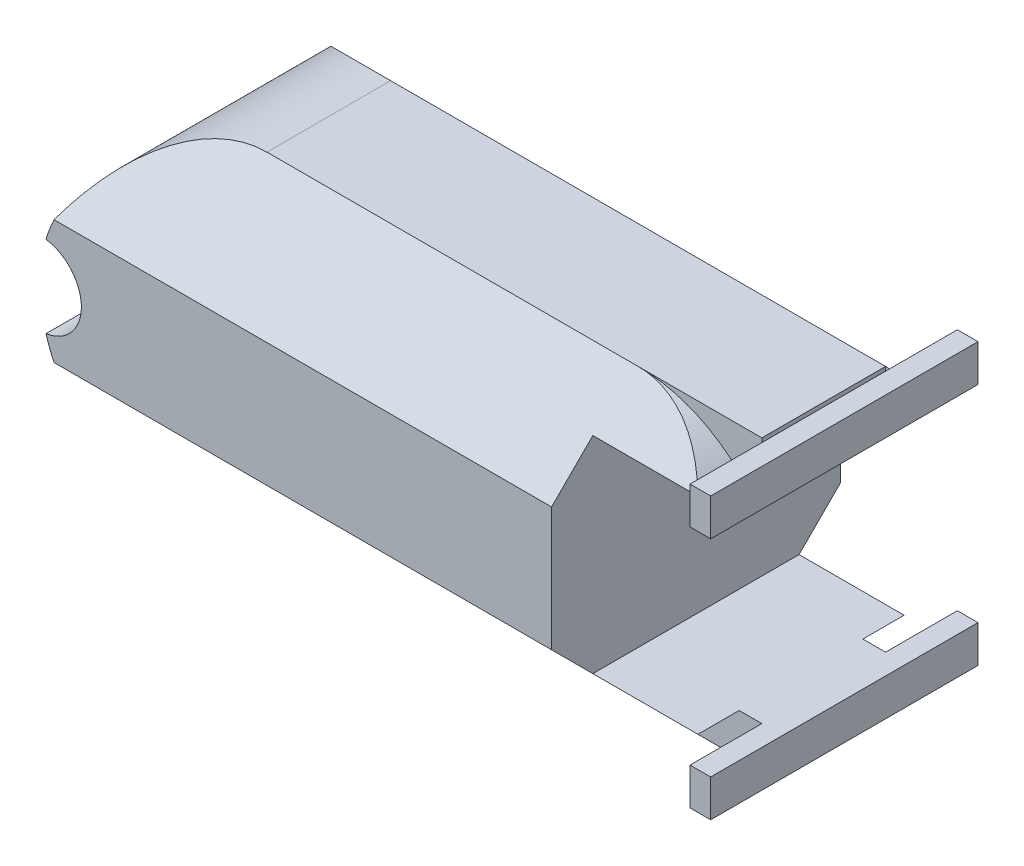
SolidWorks part; units mm, degrees
ref_plane "Ön Düzlem" through (0, 0, 0) normal (0, 0, 1) x (1, 0, 0)
ref_plane "Üst Düzlem" through (0, 0, 0) normal (0, 1, 0) x (1, 0, 0)
ref_plane "Sağ Düzlem" through (0, 0, 0) normal (1, 0, 0) x (0, 0, -1)
sketch "Çizim1" plane through (0, 0, 0) normal (0, 0, 1) x (1, 0, 0)
  line L1 (-40, 17.5) -> (40, 17.5)
  line L2 (-40, 17.5) -> (-40, -17.5)
  line L3 (-40, -17.5) -> (40, -17.5)
  line L4 (40, 17.5) -> (40, -17.5)
  line L5 (-40, 17.5) -> (40, -17.5) construction
  line L6 (-40, -17.5) -> (40, 17.5) construction
  point P0 (0, 0)
  dimension "D1" = 35
  dimension "D2" = 80
extrude "Yükseklik-Ekstrüzyon1" add sketch "Çizim1" along normal blind 35
fillet "Radyus1" radius 17.5 1 edges at (-40, 17.5, 17.5)
fillet "Radyus2" radius 17.5 1 edges at (-40, -17.5, 17.5)
fillet "Radyus3" radius 17.5 2 edges at (40, -17.5, 17.5) (40, 17.5, 17.5)
sketch "Çizim2" plane through (0, 0, 35) normal (0, 0, 1) x (1, 0, 0)
  circle A0 centre (-40, 0) radius 5
  dimension "D1" = 10
extrude "Kes-Ekstrüzyon1" cut sketch "Çizim2" against normal through all
chamfer "Pah1" distance 10 angle 45 4 edges at (0, 17.5, 35) (0, -17.5, 35) (0, -17.5, 0) (0, 17.5, 0) tangent propagation no
sketch "Çizim3" plane through (0, 17.5, 0) normal (0, 1, 0) x (1, 0, 0)
  line L0 (22.5, -10) -> (-22.5, -10) construction
  line L1 (0, -10) -> (37.5, -10)
  line L2 (0, -10) -> (0, -25)
  line L3 (0, -25) -> (37.5, -25)
  line L4 (37.5, -10) -> (37.5, -25)
  dimension "D1" = 37.5
extrude "Yükseklik-Ekstrüzyon2" add sketch "Çizim3" against normal blind 5
sketch "Çizim4" plane through (0, -17.5, 0) normal (0, -1, 0) x (1, 0, 0)
  line L0 (22.5, 25) -> (-22.5, 25) construction
  line L1 (0, 25) -> (37.5, 25)
  line L2 (0, 25) -> (0, 10)
  line L3 (0, 10) -> (37.5, 10)
  line L4 (37.5, 25) -> (37.5, 10)
  dimension "D1" = 37.5
  dimension "D2" = 15
extrude "Yükseklik-Ekstrüzyon3" add sketch "Çizim4" against normal blind 5
sketch "Çizim6" plane through (0, -12.5, 0) normal (0, 1, 0) x (1, 0, 0)
  line L0 (38.3114, -35) -> (-38.3114, -35) construction
  line L1 (40, 0) -> (22.0105, 0)
  line L2 (40, 0) -> (40, -35)
  line L3 (40, -35) -> (22.0105, -35)
  line L4 (22.0105, 0) -> (22.0105, -35)
extrude "Kes-Ekstrüzyon2" cut sketch "Çizim6" along normal blind 25
sketch "Çizim7" plane through (37.5, 0, 0) normal (1, 0, 0) x (0, 0, -1)
  line L0 (-10, 12.5) -> (-10, 17.5) construction
  line L1 (-33.7044, 17) -> (-1.2956, 17)
  line L2 (-33.7044, 17) -> (-33.7044, 12.5)
  line L3 (-33.7044, 12.5) -> (-1.2956, 12.5)
  line L4 (-1.2956, 17) -> (-1.2956, 12.5)
  line L5 (-33.7044, 17) -> (-1.2956, 12.5) construction
  line L6 (-33.7044, 12.5) -> (-1.2956, 17) construction
  line L7 (-33.7044, -12.5) -> (-1.2956, -12.5)
  line L8 (-33.7044, -12.5) -> (-33.7044, -17)
  line L9 (-33.7044, -17) -> (-1.2956, -17)
  line L10 (-1.2956, -12.5) -> (-1.2956, -17)
  line L11 (-33.7044, -12.5) -> (-1.2956, -17) construction
  line L12 (-33.7044, -17) -> (-1.2956, -12.5) construction
  line L13 (-10, -12.5) -> (-10, -17.5) construction
  line L14 (-25, 17.5) -> (-10, 17.5) construction
  line L15 (-10, -17.5) -> (-25, -17.5) construction
  point P0 (-17.5, 14.75)
  point P5 (-17.5, -14.75)
  point P10 (-10, 15)
  dimension "D1" = 32.4089
  dimension "D2" = 7.5
  dimension "D3" = 7.5
  dimension "D4" = 4.5
  dimension "D5" = 4.5
  dimension "D6" = 0.5
  dimension "D7" = 0.5
extrude "Yükseklik-Ekstrüzyon4" add sketch "Çizim7" along normal blind 2.5
